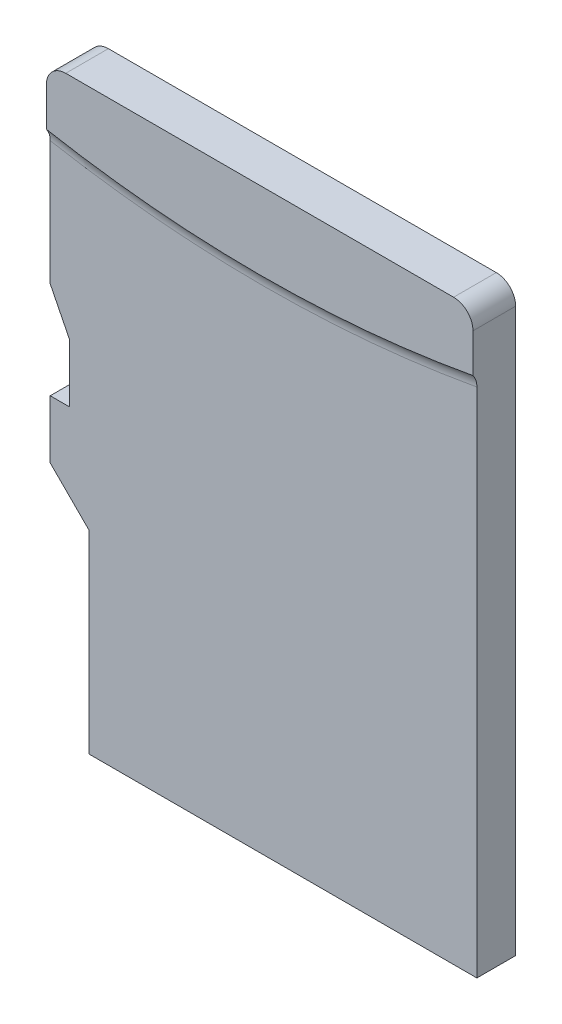
SolidWorks part; units mm, degrees
ref_plane "前视基准面" through (0, 0, 0) normal (0, 0, 1) x (1, 0, 0)
ref_plane "上视基准面" through (0, 0, 0) normal (0, 1, 0) x (1, 0, 0)
ref_plane "右视基准面" through (0, 0, 0) normal (1, 0, 0) x (0, 0, -1)
other "Configuration Table"
sketch "草图1" plane through (0, 0, 0) normal (0, 0, 1) x (1, 0, 0)
  line L0 (-5.5, 2.5) -> (-5.5, 7.5)
  line L1 (-4.5, -7.5) -> (5.5, -7.5)
  line L2 (-5.5, -1.5) -> (-5.5, 0)
  line L3 (-5.5, 7.5) -> (5.5, 7.5)
  line L4 (5.5, -7.5) -> (5.5, 7.5)
  line L5 (-4.5, -6.1364) -> (5.5, 7.5) construction
  line L6 (-5.5, 7.5) -> (5.5, -7.5) construction
  line L7 (5.5, -7.5) -> (-4.5, -7.5)
  line L8 (5.5, -7.5) -> (5.5, 7.5)
  line L9 (5.5, 7.5) -> (-4.5, 7.5)
  line L10 (-4.5, -7.5) -> (-4.5, -2.5)
  line L11 (-5.5, -1.5) -> (-4.5, -2.5)
  line L12 (-5.5, 0) -> (-5, 0)
  line L13 (-5.5, 2.5) -> (-5, 1.5)
  line L14 (-5, 0) -> (-5, 1.5)
  point P0 (0, 0)
  dimension "D1" = 11
  dimension "D3" = 10
  dimension "D5" = 5
  dimension "D7" = 1.5
  dimension "D8" = 5
extrude "凸台-拉伸1" add sketch "草图1" along normal blind 1 contours L14 L12 L2 L11 L10 L1 L4 L3 L0 L13 region at (0.2073, 0.1581, 0)
sketch "草图2" plane through (0, 0, 1) normal (0, 0, 1) x (1, 0, 0)
  line L0 (-5.5, 2.5) -> (-5.5, 7.5) construction
  line L1 (5.5, -7.5) -> (5.5, 7.5) construction
  line L2 (-5.5, 7.5) -> (5.5, 7.5) construction
  line L3 (-5.5, 6) -> (-5.5, 7.5)
  line L4 (-5.5, 7.5) -> (5.5, 7.5)
  line L5 (5.5, 7.5) -> (5.5, 6)
  arc A0 (-5.5, 6) -> (5.5, 6) centre (0, 36) ccw
  point P9 (0, 5.5)
  dimension "D1" = 2
  dimension "D2" = 1.5
extrude "凸台-拉伸2" add sketch "草图2" along normal blind 0.1
fillet "圆角1" radius 0.5 1 edges at (0, 5.5, 1)
fillet "圆角2" radius 0.5 2 edges at (-5.5, 7.5, 0.55) (5.5, 7.5, 0.55)
